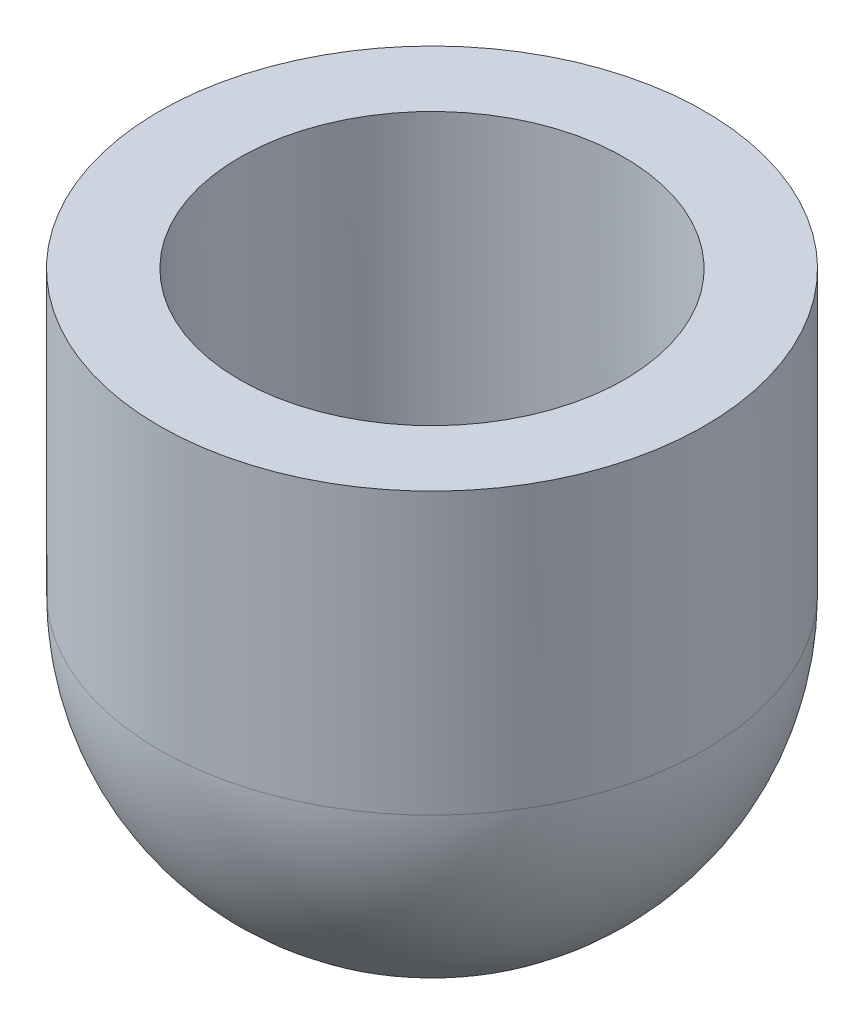
SolidWorks part; units mm, degrees
ref_plane "Front Plane" through (0, 0, 0) normal (0, 0, 1) x (1, 0, 0)
ref_plane "Top Plane" through (0, 0, 0) normal (0, 1, 0) x (1, 0, 0)
ref_plane "Right Plane" through (0, 0, 0) normal (1, 0, 0) x (0, 0, -1)
sketch "Sketch1" plane through (0, 0, 0) normal (1, 0, 0) x (0, 0, -1)
  line L0 (8.636, 0) -> (6.096, 0)
  line L1 (0, -14.986) -> (0, -17.526)
  line L2 (8.636, 0) -> (8.636, -8.89)
  line L3 (0, 26.3769) -> (0, 0) construction
  line L4 (6.096, 0) -> (6.096, -8.89)
  line L5 (0, -14.986) -> (0, -44.37) construction
  arc A1 (8.636, -8.89) -> (0, -17.526) centre (0, -8.89) cw
  arc A2 (6.096, -8.89) -> (0, -14.986) centre (0, -8.89) cw
  point P9 (0, 0)
  point P11 (0, 0)
  dimension "D5" = 6.096
  dimension "D1" = 17.526
  dimension "D2" = 8.636
  dimension "D3" = 2.54
  dimension "D4" = 8.89
  dimension "D6" = 14.986
  dimension "D7" = 6.096
revolve "Revolve1" add sketch "Sketch1" angle 360 about L3
